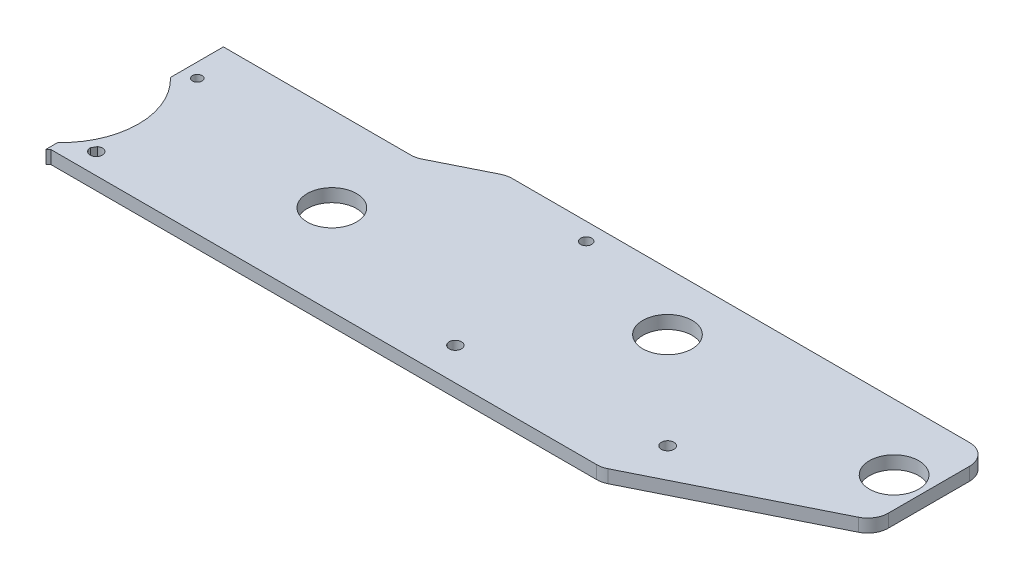
SolidWorks part; units mm, degrees
ref_plane "Front" through (0, 0, 0) normal (0, 0, 1) x (1, 0, 0)
ref_plane "Top" through (0, 0, 0) normal (0, 1, 0) x (1, 0, 0)
ref_plane "Right" through (0, 0, 0) normal (1, 0, 0) x (0, 0, -1)
sketch "Sketch1" plane through (0, 0, 0) normal (0, 1, 0) x (1, 0, 0)
  line L1 (0, 0) -> (210, 0)
  line L2 (0, 0) -> (0, -50)
  line L3 (0, -50) -> (210, -50)
  line L4 (210, 0) -> (210, -50)
  circle A7 centre (3.4895, -16.7877) radius 1.2117
  circle A8 centre (34.3726, -17.194) radius 1.1656
  circle A9 centre (37.5207, -44.9212) radius 1.5
  circle A12 centre (168.9752, -37.4032) radius 1.5173
  circle A13 centre (116, -4.2372) radius 1.3356
  circle A14 centre (12.2576, -3.2748) radius 1.6244
  dimension "D1" = 210
  dimension "D2" = 50
extrude "Boss-Extrude1" add sketch "Sketch1" along normal blind 3.175
sketch "Sketch2" plane through (0, 3.175, 0) normal (0, 1, 0) x (1, 0, 0)
  line L0 (210, 0) -> (0, 0) construction
  line L1 (0, 0) -> (0, -50) construction
  circle A0 centre (10, -26) radius 2
  circle A1 centre (10, -42) radius 2
  circle A2 centre (26, -26) radius 2
  circle A3 centre (26, -42) radius 2
  dimension "D1" = 16
  dimension "D2" = 16
  dimension "D3" = 16
  dimension "D4" = 26
  dimension "D5" = 10
  dimension "D6" = 10
  dimension "D7" = 26
  dimension "D8" = 16
extrude "Cut-Extrude1" cut sketch "Sketch2" against normal blind 10
sketch "Sketch3" plane through (0, 3.175, 0) normal (0, 1, 0) x (1, 0, 0)
  line L0 (210, 0) -> (0, 0) construction
  line L1 (210, 0) -> (0, 0) construction
  circle A0 centre (78.0103, -28.1) radius 6
  circle A1 centre (145.5313, -14) radius 6
  circle A2 centre (18, -34) radius 0.587
  circle A3 centre (26, -26) radius 2 construction
  circle A4 centre (202.6463, -16) radius 6
  dimension "D1" = 28.1
  dimension "D3" = 16
  dimension "D4" = 14
  dimension "D7" = 125.222
  dimension "D2" = 60.2996
  dimension "D5" = 8
  dimension "D6" = 8
  dimension "D8" = 57.15
extrude "Cut-Extrude2" cut sketch "Sketch3" against normal blind 57.15
sketch "Sketch4" [suppressed] plane through (0, 3.175, 0) normal (0, 1, 0) x (1, 0, 0)
  line L0 (3.4895, -16.7877) -> (18, -34)
  line L1 (3.4895, -20.6627) -> (5.9498, -23.5811)
  line L2 (18, -34) -> (34.3726, -17.194)
  line L3 (34.3726, -17.194) -> (75.8499, -28.1)
  line L4 (75.8499, -28.1) -> (37.5207, -44.9212)
  line L5 (7.3432, -17.194) -> (9.8664, -20.303)
  circle A0 centre (18, -34) radius 15.9299
  circle A1 centre (3.4895, -16.7877) radius 3.8751
  circle A2 centre (34.3726, -17.194) radius 3.7227
  circle A3 centre (37.5207, -44.9212) radius 3.8676
  circle A4 centre (75.8499, -28.1) radius 12.797
  circle A5 centre (112.3021, -4.7393) radius 5.1588
  circle A6 centre (118.879, -40.0177) radius 4.9035
  circle A7 centre (140.772, -16) radius 12.6375
  circle A8 centre (168.9752, -37.4032) radius 4.2066
  circle A9 centre (197.922, -16) radius 12.8
sketch "Sketch5" [suppressed] plane through (0, 3.175, 0) normal (0, 1, 0) x (1, 0, 0)
  line L0 (210, 0) -> (0, 0) construction
  line L2 (-0.6266, -16.7877) -> (37.5207, -16.7877)
  line L3 (-0.6266, -16.7877) -> (-0.6266, -44.9212)
  line L4 (-0.6266, -44.9212) -> (37.5207, -44.9212)
  line L5 (37.5207, -16.7877) -> (37.5207, -44.9212)
  line L6 (75.8499, -15.182) -> (37.5207, -15.182)
  line L7 (75.8499, -15.182) -> (75.8499, -44.9212)
  line L8 (75.8499, -44.9212) -> (37.5207, -44.9212)
  line L9 (37.5207, -15.182) -> (37.5207, -44.9212)
  line L10 (112.3021, -4.7393) -> (75.8499, -4.7393)
  line L11 (112.3021, -4.7393) -> (112.3021, -44.9212)
  line L12 (112.3021, -44.9212) -> (75.8499, -44.9212)
  line L13 (75.8499, -4.7393) -> (75.8499, -44.9212)
  line L14 (112.3021, -4.7393) -> (102.3945, -4.7393)
  line L16 (112.3021, -4.7393) -> (112.3021, 0)
  line L17 (112.3021, 0) -> (102.3945, 0)
  line L18 (102.3945, -4.7393) -> (102.3945, 0)
  line L19 (210, -50) -> (210, 0) construction
  line L20 (112.3021, -4.7393) -> (123.1553, -4.7393)
  line L21 (112.3021, -4.7393) -> (112.3021, 0)
  line L22 (112.3021, 0) -> (123.1553, 0)
  line L23 (123.1553, -4.7393) -> (123.1553, 0)
  line L24 (112.3021, -4.7393) -> (140.772, -4.7393)
  line L25 (112.3021, -4.7393) -> (112.3021, -40.0177)
  line L26 (112.3021, -40.0177) -> (140.772, -40.0177)
  line L27 (140.772, -4.7393) -> (140.772, -40.0177)
  line L28 (140.772, -16) -> (168.9752, -16)
  line L29 (140.772, -16) -> (140.772, -40.0177)
  line L30 (140.772, -40.0177) -> (168.9752, -40.0177)
  line L31 (168.9752, -16) -> (168.9752, -40.0177)
  line L32 (168.9752, -4.7393) -> (210, -4.7393)
  line L33 (168.9752, -4.7393) -> (168.9752, -40.0177)
  line L34 (168.9752, -40.0177) -> (210, -40.0177)
  line L35 (210, -4.7393) -> (210, -40.0177)
  line L36 (0, -50) -> (210, -50) construction
  line L37 (160.7629, -40.0177) -> (177.2091, -40.0177)
  line L38 (160.7629, -40.0177) -> (160.7629, -44.9212)
  line L39 (160.7629, -44.9212) -> (177.2091, -44.9212)
  line L40 (177.2091, -40.0177) -> (177.2091, -44.9212)
  line L41 (112.3021, -40.0177) -> (126.3591, -40.0177)
  line L42 (112.3021, -40.0177) -> (112.3021, -47.7828)
  line L43 (112.3021, -47.7828) -> (126.3591, -47.7828)
  line L44 (126.3591, -40.0177) -> (126.3591, -47.7828)
  line L45 (30.5963, -44.9212) -> (44.6115, -44.9212)
  line L46 (30.5963, -44.9212) -> (30.5963, -50)
  line L47 (30.5963, -50) -> (44.6115, -50)
  line L48 (44.6115, -44.9212) -> (44.6115, -50)
  line L50 (-0.6266, -44.9212) -> (30.5963, -44.9212)
  line L51 (-0.6266, -44.9212) -> (-0.6266, -50)
  line L52 (-0.6266, -50) -> (30.5963, -50)
  line L53 (30.5963, -44.9212) -> (30.5963, -50)
  circle A0 centre (3.4895, -16.7877) radius 4.1161
  circle A1 centre (34.3726, -17.194) radius 3.8132
  circle A2 centre (75.8499, -28.1) radius 12.918
  circle A3 centre (112.3021, -4.7393) radius 5.2663
  circle A4 centre (140.772, -16) radius 13.0245
  circle A5 centre (197.922, -16) radius 12.3805
  circle A6 centre (168.9752, -37.4032) radius 4.7643
  circle A7 centre (118.879, -40.0177) radius 5.279
  circle A8 centre (37.5207, -44.9212) radius 4.2049
  line M12 (0, 0) -> (0, -50)
  line M13 (0, -50) -> (210, -50)
  line M14 (210, -50) -> (210, 0)
  line M15 (210, 0) -> (0, 0)
extrude "Cut-Extrude5" [suppressed] cut sketch "Sketch5" against normal blind 11.52 contours A5 L32 L23 L24 A4 L28 L33 M14 M15 | A1 L6 L13 L10 L18 A0 L2 M15 M12 | L8 L48 L34 L40 L39 L38 L30 L26 L44 L43 L42 L12 M13 M14
fillet "Fillet1" [suppressed] radius 5
sketch "Sketch10" plane through (0, 3.175, 0) normal (0, 1, 0) x (1, 0, 0)
  line L0 (210, -27.8594) -> (165.5029, -50)
  line L1 (210, -50) -> (210, 0) construction
  line L2 (0, -50) -> (210, -50) construction
  line L3 (165.5029, -50) -> (210, -50)
  line L4 (210, -50) -> (210, -27.8594)
  line L5 (92.5326, 0) -> (77.6548, -7.4028)
  line L6 (210, 0) -> (0, 0) construction
  line L7 (77.6548, -7.4028) -> (0, -7.4028)
  line L8 (0, 0) -> (0, -50) construction
  line L9 (0, -7.4028) -> (0, 0)
  line L10 (0, 0) -> (92.5326, 0)
extrude "Cut-Extrude7" cut sketch "Sketch10" against normal blind 10
fillet "Fillet3" radius 5 7 edges at (0, 1.5875, 50) (0, 1.5875, 7.4028) (77.6548, 1.5875, 7.4028) (92.5326, 1.5875, 0) (210, 1.5875, 0) (210, 1.5875, 27.8594) (165.5029, 1.5875, 50)
sketch "Sketch11" plane through (0, 3.175, 0) normal (0, 1, 0) x (1, 0, 0)
  circle A0 centre (18, -34) radius 18.5
  circle A1 centre (10, -26) radius 2
  circle A2 centre (10, -42) radius 2
  circle A3 centre (26, -26) radius 2
  circle A4 centre (26, -42) radius 2
extrude "Boss-Extrude4" add sketch "Sketch11" against normal blind 3.175
sketch "Sketch12" plane through (0, 3.175, 0) normal (0, 1, 0) x (1, 0, 0)
  circle A0 centre (18, -34) radius 21
  circle A1 centre (10, -26) radius 2 construction
  circle A2 centre (10, -42) radius 2 construction
  dimension "D1" = 8
  dimension "D2" = 8
extrude "Boss-Extrude5" add sketch "Sketch12" against normal blind 3.175
sketch "Sketch13" plane through (0, 3.175, 0) normal (0, 1, 0) x (1, 0, 0)
  circle A0 centre (18, -34) radius 18.85
extrude "Cut-Extrude8" cut sketch "Sketch13" against normal blind 3.175
sketch "Sketch14" plane through (0, 3.175, 0) normal (0, 1, 0) x (1, 0, 0)
  line L0 (0, -12.4028) -> (0, -23.1833) construction
  line L1 (0, -34.2728) -> (-35.83, -34.2728)
  line L2 (0, -34.2728) -> (0, 0.7272)
  line L3 (0, 0.7272) -> (-35.83, 0.7272)
  line L4 (-35.83, -34.2728) -> (-35.83, 0.7272)
  line L5 (5, -7.4028) -> (76.4796, -7.4028) construction
  line L8 (0, 0.7272) -> (18, 0.7272)
  line L9 (0, 0.7272) -> (0, -12.2485)
  line L10 (0, -12.2485) -> (18, -12.2485)
  line L11 (18, 0.7272) -> (18, -12.2485)
  line M20 (76.4796, -7.4028) -> (5, -7.4028)
  arc M21 (5, -7.4028) -> (0, -12.4028) centre (5, -12.4028) ccw
  line M22 (0, -12.4028) -> (0, -23.1833)
  arc M23 (0, -23.1833) -> (0, -44.8167) centre (18, -34) ccw
  dimension "D4" = 18
  dimension "D1" = 8.13
  dimension "D2" = 35.83
  dimension "D3" = 35
extrude "Boss-Extrude6" add sketch "Sketch14" against normal blind 3.175 contours L4 L1 L2 L3 M23 M22 | L11 L8 L2 L10 M21 M20 region at (-18.2239, 3.175, 16.5271) region at (8.7212, 3.175, 3.5211)
fillet "Fillet4" radius 5 3 edges at (18, 1.5875, -0.7272) (-35.83, 1.5875, 34.2728) (-35.83, 1.5875, -0.7272)
sketch "Sketch15" plane through (0, 3.175, 0) normal (0, 1, 0) x (1, 0, 0)
  line L0 (210, -24.7625) -> (210, -5) construction
  circle A0 centre (122, -42.0581) radius 1.5
  dimension "D1" = 88
extrude "Cut-Extrude9" cut sketch "Sketch15" against normal blind 10
sketch "Sketch16" plane through (0, 3.175, 0) normal (0, 1, 0) x (1, 0, 0)
  line L0 (18, -4.2728) -> (18, -7.4028) construction
  line L1 (13, 0.7272) -> (-30.83, 0.7272) construction
  circle A0 centre (12, -3.2728) radius 1.5
  dimension "D1" = 6
  dimension "D2" = 4
extrude "Cut-Extrude10" cut sketch "Sketch16" against normal blind 10
sketch "Sketch17" plane through (0, 3.175, 0) normal (0, 1, 0) x (1, 0, 0)
  line L3 (-51.8835, 9.8769) -> (30.9276, 9.8769)
  line L4 (-51.8835, 9.8769) -> (-51.8835, -56.6458)
  line L5 (-51.8835, -56.6458) -> (30.9276, -56.6458)
  line L6 (30.9276, 9.8769) -> (30.9276, -56.6458)
extrude "Cut-Extrude11" cut sketch "Sketch17" against normal blind 10 contours L4 L5 L6 L3
